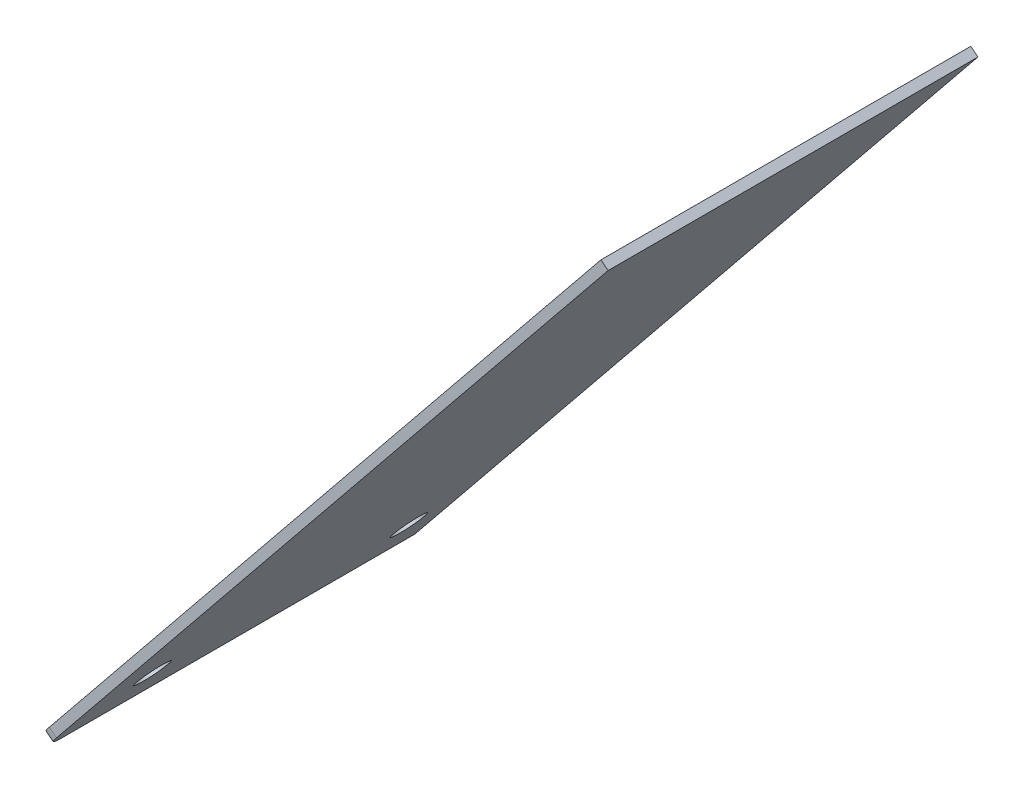
SolidWorks part; units mm, degrees
ref_plane "Front Plane" through (0, 0, 0) normal (0, 0, 1) x (1, 0, 0)
ref_plane "Top Plane" through (0, 0, 0) normal (0, 1, 0) x (1, 0, 0)
ref_plane "Right Plane" through (0, 0, 0) normal (1, 0, 0) x (0, 0, -1)
sketch "Sketch1" plane through (0, 0, 0) normal (0, 0, 1) x (1, 0, 0)
  line L0 (-117.475, -3.175) -> (-606.425, -606.425) construction
  line L1 (-112.5419, -7.1734) -> (-117.475, -3.175)
  line L2 (-117.475, -3.175) -> (-507.9403, -484.9179)
  line L3 (-507.9403, -484.9179) -> (-503.0072, -488.9162)
  line L4 (-503.0072, -488.9162) -> (-112.5419, -7.1734)
  line L6 (-606.425, -390.8989) -> (-390.8989, -606.425) construction
  circle A0 centre (-606.425, -606.425) radius 77.0255 construction
  point P3 (-509.9395, -487.3844)
  dimension "D1" = 6.35
  dimension "D2" = 3.175
extrude "Boss-Extrude1" add sketch "Sketch1" along normal up to surface (256.54 mm away)
sketch "Sketch2" plane through (-69.3451, 56.206, 0) normal (-0.7769, 0.6297, 0) x (0, 0, 1)
  circle A0 centre (36.195, -645.7492) radius 11.1125 construction
  circle A1 centre (36.195, -645.7492) radius 11.1125
  circle A2 centre (213.995, -645.7492) radius 11.1125 construction
  circle A3 centre (213.995, -645.7492) radius 11.1125
extrude "Cut-Extrude1" cut sketch "Sketch2" against normal up to next
fillet "Fillet1" radius 12.7 1 edges at (-505.4737, -486.9171, 256.54)
